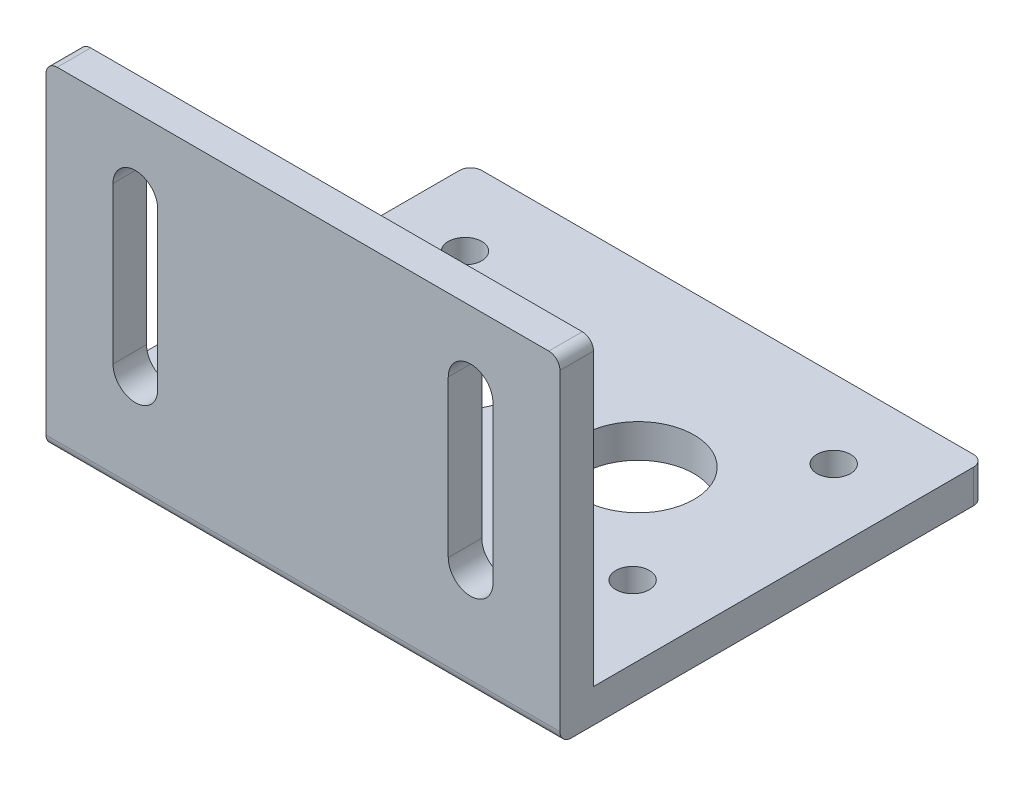
SolidWorks part; units mm, degrees
ref_plane "Front Plane" through (0, 0, 0) normal (0, 0, 1) x (1, 0, 0)
ref_plane "Top Plane" through (0, 0, 0) normal (0, 1, 0) x (1, 0, 0)
ref_plane "Right Plane" through (0, 0, 0) normal (1, 0, 0) x (0, 0, -1)
sketch "Sketch2" plane through (0, 0, 0) normal (0, 1, 0) x (1, 0, 0)
  line L0 (8, 19) -> (8, 3) construction
  line L1 (-22, 19) -> (22, 19)
  line L2 (-23, 18) -> (-23, -19)
  line L3 (-23, -19) -> (23, -19)
  line L4 (23, 18) -> (23, -19)
  line L5 (-23, 19) -> (23, -19) construction
  line L6 (-23, -19) -> (23, 19) construction
  line L7 (8, 3) -> (23, 3) construction
  line L8 (0, 19) -> (0, -19) construction
  line L9 (-23, 3) -> (23, 3) construction
  circle A0 centre (8, 3) radius 5
  circle A1 centre (-8, 3) radius 5
  circle A2 centre (-16.5, 12) radius 1.5
  circle A3 centre (-16.5, -6) radius 1.5
  circle A4 centre (16.5, -6) radius 1.5
  circle A5 centre (16.5, 12) radius 1.5
  arc A6 (23, 18) -> (22, 19) centre (22, 18) ccw
  arc A7 (-22, 19) -> (-23, 18) centre (-22, 18) ccw
  point P0 (0, 0)
  dimension "D5" = 16.5
  dimension "D7" = 1
  dimension "D1" = 46
  dimension "D2" = 38
  dimension "D3" = 16
  dimension "D4" = 15
  dimension "D6" = 9
extrude "Boss-Extrude1" add sketch "Sketch2" along normal blind 3
sketch "Sketch3" plane through (0, 3, 0) normal (0, 1, 0) x (1, 0, 0)
  line L0 (0, 19) -> (0, -19) construction
  line L1 (22, 19) -> (-22, 19) construction
  line L2 (-23, -19) -> (23, -19) construction
  line L3 (23, -19) -> (23, 18) construction
  line L4 (-23, -19) -> (23, -19)
  line L5 (-23, -19) -> (-23, -16)
  line L6 (-23, -16) -> (23, -16)
  line L7 (23, -19) -> (23, -16)
  dimension "3" = 3
extrude "Boss-Extrude2" add sketch "Sketch3" along normal blind 27
sketch "Sketch4" plane through (0, 0, 16) normal (0, 0, -1) x (-1, 0, 0)
  line L0 (0, 30) -> (0, 3) construction
  line L1 (-23, 30) -> (23, 30) construction
  line L2 (-22, 3) -> (22, 3) construction
  line L3 (-23, 23.5) -> (23, 23.5) construction
  line L4 (-23, 30) -> (-23, 3) construction
  line L5 (23, 30) -> (23, 3) construction
  line L6 (-15, 30) -> (-15, 3) construction
  line L7 (-17, 23.5) -> (-17, 9.5)
  line L8 (-13, 23.5) -> (-13, 9.5)
  line L9 (13, 23.5) -> (13, 9.5)
  line L10 (17, 23.5) -> (17, 9.5)
  arc A2 (-13, 23.5) -> (-17, 23.5) centre (-15, 23.5) ccw
  arc A3 (-13, 9.5) -> (-17, 9.5) centre (-15, 9.5) cw
  arc A4 (13, 23.5) -> (17, 23.5) centre (15, 23.5) cw
  arc A5 (13, 9.5) -> (17, 9.5) centre (15, 9.5) ccw
  dimension "D1" = 6.5
  dimension "D2" = 15
extrude "Cut-Extrude1" cut sketch "Sketch4" against normal through all
fillet "Fillet1" radius 1 2 edges at (-23, 30, 17.5) (23, 30, 17.5)
fillet "Fillet2" radius 1 1 edges at (0, 0, 19)
